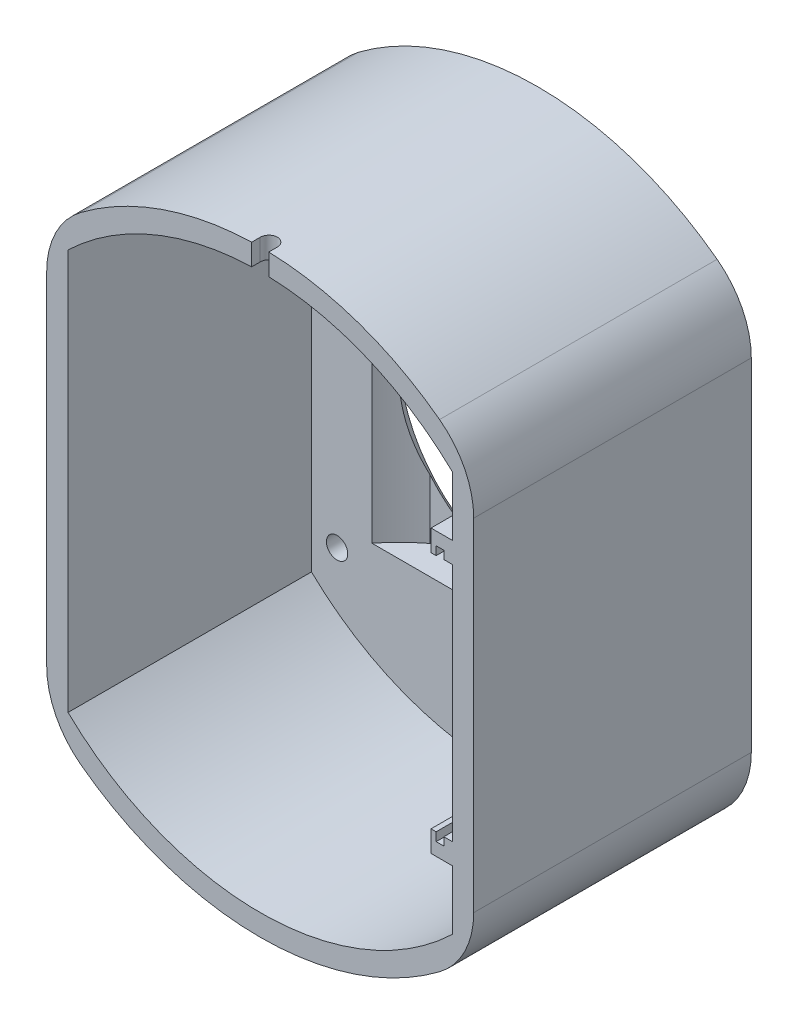
SolidWorks part; units mm, degrees
ref_plane "Спереди" through (0, 0, 0) normal (0, 0, 1) x (1, 0, 0)
ref_plane "Сверху" through (0, 0, 0) normal (0, 1, 0) x (1, 0, 0)
ref_plane "Справа" through (0, 0, 0) normal (1, 0, 0) x (0, 0, -1)
sketch "Эскиз1" plane through (0, 0, 0) normal (0, 0, 1) x (1, 0, 0)
  line L1 (45, -46.9042) -> (45, 46.9042)
  line L2 (0, 0) -> (0, -65) construction
  line L3 (50, -48.9898) -> (50, 48.9898)
  line L4 (-50, -48.9898) -> (-50, 48.9898)
  line L5 (-45, -46.9042) -> (-45, 46.9042)
  line L6 (-29.0575, -58.1435) -> (-29.0575, -34.0575)
  line L7 (-34.0575, -29.0575) -> (-45, -29.0575)
  line L8 (34.0575, -29.0575) -> (45, -29.0575)
  line L9 (29.0575, -58.1435) -> (29.0575, -34.0575)
  line L10 (34.0575, 29.0575) -> (45, 29.0575)
  line L11 (-39, -39) -> (39, 39) construction
  line L12 (-39, 39) -> (39, -39) construction
  line L13 (29.0575, 58.1435) -> (29.0575, 34.0575)
  line L14 (-34.0575, 29.0575) -> (-45, 29.0575)
  line L15 (-29.0575, 58.1435) -> (-29.0575, 34.0575)
  line L16 (-0.1, 27.5) -> (0.1, 27.5)
  line L17 (-27.5, -27.5) -> (27.5, -27.5) construction
  line L18 (-27.5, -27.5) -> (-27.5, 27.5) construction
  line L19 (-27.5, 27.5) -> (27.5, 27.5) construction
  line L20 (27.5, -27.5) -> (27.5, 27.5) construction
  line L21 (-27.5, -27.5) -> (27.5, 27.5) construction
  line L22 (-27.5, 27.5) -> (27.5, -27.5) construction
  line L23 (-27.5, 0.1) -> (-27.5, -0.1)
  line L24 (-0.1, -27.5) -> (0.1, -27.5)
  line L25 (27.5, 0.1) -> (27.5, -0.1)
  line L26 (-27.5, 27.5) -> (27.5, -27.5) construction
  line L27 (-27.5, -27.5) -> (27.5, 27.5) construction
  arc A0 (-45, -46.9042) -> (45, -46.9042) centre (0, 0) ccw
  arc A1 (50, 48.9898) -> (-50, 48.9898) centre (0, 0) ccw
  arc A2 (45, 46.9042) -> (-45, 46.9042) centre (0, 0) ccw
  circle A3 centre (0, 0) radius 65 construction
  circle A4 centre (0, 0) radius 70 construction
  arc A5 (-50, -48.9898) -> (50, -48.9898) centre (0, 0) ccw
  circle A6 centre (-39, -39) radius 2.5
  arc A7 (-29.0575, -34.0575) -> (-34.0575, -29.0575) centre (-34.0575, -34.0575) ccw
  circle A8 centre (39, -39) radius 2.5
  arc A9 (29.0575, -34.0575) -> (34.0575, -29.0575) centre (34.0575, -34.0575) cw
  circle A10 centre (39, 39) radius 2.5
  arc A11 (29.0575, 34.0575) -> (34.0575, 29.0575) centre (34.0575, 34.0575) ccw
  circle A12 centre (-39, 39) radius 2.5
  arc A13 (-29.0575, 34.0575) -> (-34.0575, 29.0575) centre (-34.0575, 34.0575) cw
  arc A14 (-27.5, -0.1) -> (-0.1, -27.5) centre (-0.1, -0.1) ccw
  arc A15 (-0.1, 27.5) -> (-27.5, 0.1) centre (-0.1, 0.1) ccw
  arc A16 (0.1, 27.5) -> (27.5, 0.1) centre (0.1, 0.1) cw
  arc A17 (0.1, -27.5) -> (27.5, -0.1) centre (0.1, -0.1) ccw
  point P4 (66.9413, 20.466)
  point P14 (65, 0)
  point P26 (-29.0575, -29.0575)
  dimension "D2" = 140
  dimension "D6" = 5
  dimension "D7" = 5
  dimension "D11" = 27.4
  dimension "D3" = 5
  dimension "D4" = 78
  dimension "D5" = 78
  dimension "D8" = 55
  dimension "D9" = 55
  dimension "D10" = 100
  dimension "D1" = 5
extrude "Extrude" add sketch "Эскиз1" along normal blind 65 contours L4 A5 L3 A1 A2 L1 A0 L5 region at (0, -68.2795, 0)
extrude "Boss-Extrude1" add sketch "Эскиз1<3>" along normal blind 8 contours L6 A7 L7 L5 A0 A6 | A9 L9 A0 L1 L8 A8 | L13 A11 L10 L1 A2 A10 | A15 A13 L15 A2 L5 L14 A12 | A15 A13 L14 L5 L7 A7 A14 L23 | A17 L24 A14 A7 L6 A0 L9 A9 | A17 A9 L8 L1 L10 A11 A16 L25 | L16 A16 A11 L13 A2 L15 A13 A15 region at (36.3642, -41.6012, 0) region at (39.5287, -27.4763, 0) region at (36.3642, 41.6012, 0) region at (-36.3642, -41.6012, 0) region at (-36.3642, 41.6012, 0)
sketch "Эскиз1<3>" plane through (0, 0, 0) normal (0, 0, 1) x (1, 0, 0) same geometry as "Эскиз1"
fillet "Fillet1" radius 20 4 edges at (50, -48.9898, 32.5) (-50, -48.9898, 32.5) (-50, 48.9898, 32.5) (50, 48.9898, 32.5)
chamfer "Chamfer3" distance 5 angle 45 8 edges at (27.5, 0, 0) (19.4747, 19.4747, 0) (19.4747, -19.4747, 0) (0, 27.5, 0) (0, -27.5, 0) (-19.4747, 19.4747, 0) (-19.4747, -19.4747, 0) (-27.5, 0, 0)
sketch "Sketch3" plane through (0, 0, 65) normal (0, 0, 1) x (1, 0, 0)
  line L0 (0, 0) -> (45, 0) construction
  line L1 (41.2, -28) -> (43, -28.1045)
  line L2 (45, -46.9042) -> (45, 46.9042) construction
  line L3 (45, 33) -> (40, 33)
  line L4 (40, 33) -> (40, 28)
  line L5 (40, 28) -> (41.2, 28)
  line L6 (41.2, 28) -> (41.2, 30)
  line L7 (41.2, 30) -> (43, 30)
  line L8 (43, 30) -> (43, 28.1045)
  line L9 (43, 28.1045) -> (45, 28.1045)
  line L10 (45, 28.1045) -> (45, 33)
  line L11 (43, -28.1045) -> (45, -28.1045)
  line L12 (43, -30) -> (43, -28.1045)
  line L13 (41.2, -30) -> (43, -30)
  line L14 (41.2, -28) -> (41.2, -30)
  line L15 (40, -28) -> (41.2, -28)
  line L16 (40, -33) -> (40, -28)
  line L17 (45, -33) -> (40, -33)
  line L18 (45, -28.1045) -> (45, -33)
  line L19 (41.2, 28) -> (43, 28.1045)
  point P7 (42.1, 30)
  dimension "D1" = 1.8
  dimension "D2" = 5
  dimension "D3" = 3
  dimension "D4" = 30
  dimension "D5" = 5
  dimension "D6" = 2
extrude "Boss-Extrude3" add sketch "Sketch3" against normal blind 10 contours L18 L12 L13 L14 L16 L17 | L16 L14 L15 | L10 L3 L4 L6 L7 L8 | L5 L6 L4 region at (42.5532, -30.779, 65) region at (42.5532, 30.779, 65)
extrude "Boss-Extrude4" add sketch "Sketch3<2>" along normal blind 10 from offset 45 contours L18 L12 L13 L14 L16 L17 | L16 L14 L15 | L10 L3 L4 L6 L7 L8 | L5 L6 L4 region at (42.5532, -30.779, 65) region at (42.5532, 30.779, 65) offset against normal yes
sketch "Sketch3<2>" plane through (0, 0, 65) normal (0, 0, 1) x (1, 0, 0) same geometry as "Sketch3"
sketch "Sketch5" plane through (0, 0, 0) normal (0, 1, 0) x (1, 0, 0)
  line L0 (0, 0) -> (0, -65) construction
  line L1 (-42, -65) -> (42, -65) construction
  line L2 (-2, -63) -> (-2, -65)
  line L3 (-2, -65) -> (2, -65)
  line L4 (2, -65) -> (2, -63)
  arc A0 (2, -63) -> (-2, -63) centre (0, -63) ccw
  circle A1 centre (5, -55) radius 1.1
  circle A2 centre (-5, -55) radius 1.1
  dimension "D1" = 4
  dimension "D2" = 2
  dimension "D3" = 2.2
  dimension "D4" = 5
  dimension "D5" = 10
extrude "Cut-Extrude2" cut sketch "Sketch5" along normal through all contours A0 L0 L3 L4 | L0 A0 L2 L3 region at (0.9335, 0, 63.1867) region at (-0.9335, 0, 63.1867)
extrude "Cut-Extrude3" cut sketch "Sketch5<4>" along normal blind 68 contours A2 | A1
sketch "Sketch5<4>" plane through (0, 0, 0) normal (0, 1, 0) x (1, 0, 0) same geometry as "Sketch5"
sketch "Sketch6" plane through (0, 0, 0) normal (0, 1, 0) x (1, 0, 0)
  line L0 (0, 0) -> (0, -65) construction
  line L1 (-45, -65) -> (45, -65) construction
  line L2 (-24, -1.25) -> (24, -1.25)
  line L3 (-45, -8) -> (45, -8) construction
  line L4 (30.8596, -8) -> (-0.1, -8)
  line L5 (-30.8596, -8) -> (0.1, -8)
  line L6 (42, 0) -> (-42, 0) construction
  arc A0 (24, -1.25) -> (30.8596, -8) centre (0, -32.5) cw
  arc A1 (-24, -1.25) -> (-30.8596, -8) centre (0, -32.5) ccw
  point P7 (0, -32.5)
  point P17 (0, -1.25)
  dimension "D1" = 24
  dimension "D2" = 1.25
extrude "Cut-Extrude4" cut sketch "Sketch6" against normal mid plane 68 contours L2 L0 L4 A0 | L0 L2 A1 L5 region at (13.9253, 0, 4.7634) region at (-13.9253, 0, 4.7634)
chamfer "Chamfer4" distance 2 angle 45 4 edges at (41.5, 39, 0) (-36.5, 39, 0) (-36.5, -39, 0) (41.5, -39, 0)
